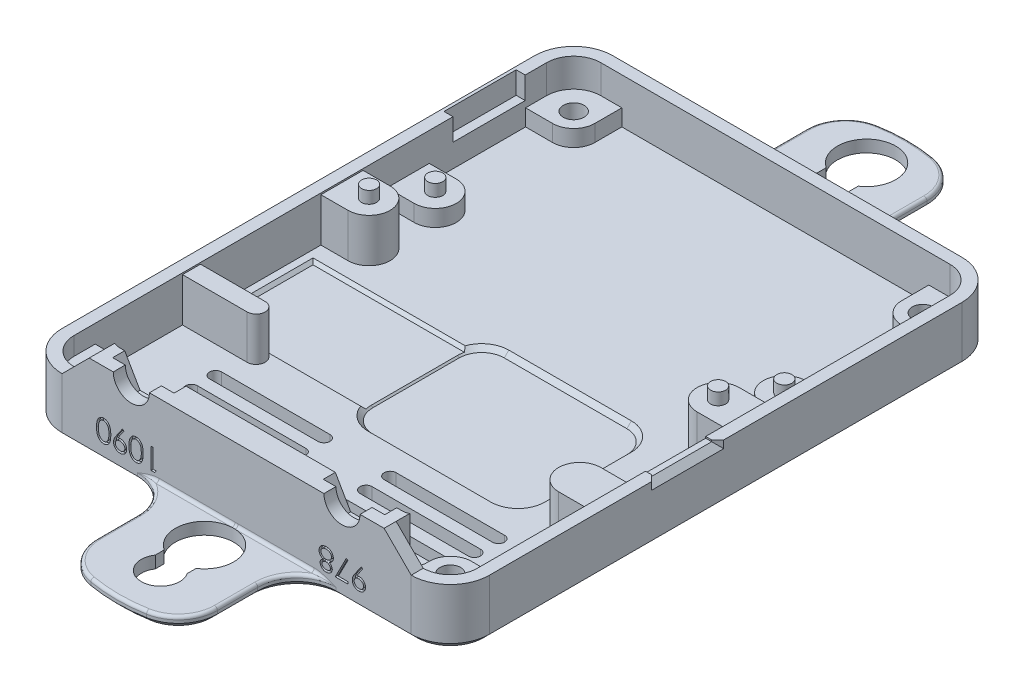
SolidWorks part; units mm, degrees
ref_plane "Front Plane" through (0, 0, 0) normal (0, 0, 1) x (1, 0, 0)
ref_plane "Top Plane" through (0, 0, 0) normal (0, 1, 0) x (1, 0, 0)
ref_plane "Right Plane" through (0, 0, 0) normal (1, 0, 0) x (0, 0, -1)
sketch "Sketch1" plane through (0, 0, 0) normal (0, 1, 0) x (1, 0, 0)
  line L0 (-33.8462, -25.5532) -> (31.1538, -25.5532)
  line L1 (-33.8462, 38.4468) -> (31.1538, 38.4468)
  line L2 (-33.8462, 38.4468) -> (-33.8462, 8.4468)
  line L3 (-33.8462, 8.4468) -> (31.1538, 8.4468)
  line L4 (31.1538, 38.4468) -> (31.1538, 8.4468)
  line L5 (-30.3462, 34.9468) -> (27.6538, 34.9468)
  line L6 (-30.3462, 34.9468) -> (-30.3462, 11.9468)
  line L7 (-30.3462, 11.9468) -> (27.6538, 11.9468)
  line L8 (27.6538, 34.9468) -> (27.6538, 11.9468)
  line L9 (-30.3462, 0.9468) -> (27.6538, 0.9468)
  line L10 (-30.3462, 0.9468) -> (-30.3462, -22.0532)
  line L11 (-33.8462, 4.4468) -> (31.1538, 4.4468)
  line L12 (-33.8462, 4.4468) -> (-33.8462, -25.5532)
  line L13 (-30.3462, -22.0532) -> (27.6538, -22.0532)
  line L14 (31.1538, 4.4468) -> (31.1538, -25.5532)
  line L15 (27.6538, 0.9468) -> (27.6538, -22.0532)
  line L16 (-37.9161, 25.3468) -> (-35.3276, 25.3468)
  line L17 (7.5538, 7.5472) -> (7.5538, 6.2645)
  line L18 (20.1538, 7.5472) -> (20.1538, 6.2645)
  dimension "D1" = 65
  dimension "D2" = 30
  dimension "D3" = 58
  dimension "D4" = 23
  dimension "D5" = 3.5
  dimension "D6" = 3.5
  dimension "D7" = 65
  dimension "D8" = 30
  dimension "D9" = 58
  dimension "D10" = 23
  dimension "D11" = 3.5
  dimension "D12" = 3.5
  dimension "D13" = 4
  dimension "D14" = 16.9
  dimension "D15" = 41.4
  dimension "D16" = 54
sketch "Sketch2" plane through (0, 0, 0) normal (0, 1, 0) x (1, 0, 0)
  line L0 (-33.8462, 38.4468) -> (-33.8462, 8.4468) construction
  line L1 (-30.3462, 39.4468) -> (27.6538, 39.4468)
  line L2 (-34.8462, 34.9468) -> (-34.8462, -43.5532)
  line L3 (-30.3462, -48.0532) -> (27.6538, -48.0532)
  line L4 (32.1538, 34.9468) -> (32.1538, -43.5532)
  line L5 (-33.8462, 38.4468) -> (31.1538, 38.4468) construction
  line L6 (31.1538, 38.4468) -> (31.1538, 8.4468) construction
  line L7 (-30.3462, 41.4468) -> (27.6538, 41.4468)
  line L8 (34.1538, 34.9468) -> (34.1538, -43.5532)
  line L9 (-30.3462, -50.0532) -> (27.6538, -50.0532)
  line L10 (-36.8462, 34.9468) -> (-36.8462, -43.5532)
  line L11 (-34.8462, 39.4468) -> (32.1538, 39.4468) construction
  line L12 (-34.8462, 39.4468) -> (-34.8462, -48.0532) construction
  line L13 (-36.8462, 41.4468) -> (-36.8462, -50.0532) construction
  line L14 (-36.8462, 41.4468) -> (34.1538, 41.4468) construction
  line L15 (32.1538, 39.4468) -> (32.1538, -48.0532) construction
  line L16 (34.1538, 41.4468) -> (34.1538, -50.0532) construction
  line L17 (-36.8462, -50.0532) -> (34.1538, -50.0532) construction
  line L18 (-34.8462, -48.0532) -> (32.1538, -48.0532) construction
  arc A0 (-30.3462, 39.4468) -> (-34.8462, 34.9468) centre (-30.3462, 34.9468) ccw
  arc A1 (-36.8462, 34.9468) -> (-30.3462, 41.4468) centre (-30.3462, 34.9468) cw
  arc A2 (32.1538, 34.9468) -> (27.6538, 39.4468) centre (27.6538, 34.9468) ccw
  arc A3 (34.1538, 34.9468) -> (27.6538, 41.4468) centre (27.6538, 34.9468) ccw
  arc A4 (27.6538, -50.0532) -> (34.1538, -43.5532) centre (27.6538, -43.5532) ccw
  arc A5 (-36.8462, -43.5532) -> (-30.3462, -50.0532) centre (-30.3462, -43.5532) ccw
  arc A6 (27.6538, -48.0532) -> (32.1538, -43.5532) centre (27.6538, -43.5532) ccw
  arc A7 (-30.3462, -48.0532) -> (-34.8462, -43.5532) centre (-30.3462, -43.5532) cw
  dimension "D6" = 4.5
  dimension "D7" = 6.5
  dimension "D8" = 4.5
  dimension "D9" = 6.5
  dimension "D10" = 6.5
  dimension "D11" = 4.5
  dimension "D1" = 1
  dimension "D2" = 1
  dimension "D3" = 1
  dimension "D4" = 87.5
  dimension "D5" = 2
extrude "Boss-Extrude1" add sketch "Sketch2" along normal blind 9.5
sketch "Sketch3" plane through (0, 0, 0) normal (0, 1, 0) x (1, 0, 0)
  line L0 (-30.3462, -48.0532) -> (27.6538, -48.0532)
  line L1 (-30.3462, 39.4468) -> (27.6538, 39.4468)
  line L2 (-34.8462, 34.9468) -> (-34.8462, -43.5532)
  line L4 (32.1538, 34.9468) -> (32.1538, -43.5532)
  arc A0 (-34.8462, -43.5532) -> (-30.3462, -48.0532) centre (-30.3462, -43.5532) ccw
  arc A1 (27.6538, -48.0532) -> (32.1538, -43.5532) centre (27.6538, -43.5532) ccw
  arc A2 (32.1538, 34.9468) -> (27.6538, 39.4468) centre (27.6538, 34.9468) ccw
  arc A3 (-30.3462, 39.4468) -> (-34.8462, 34.9468) centre (-30.3462, 34.9468) ccw
  dimension "D1" = 4.5
  dimension "D2" = 4.5
  dimension "D3" = 87.5
extrude "Boss-Extrude2" add sketch "Sketch3" along normal blind 2
sketch "Sketch4" plane through (0, 2, 0) normal (0, 1, 0) x (1, 0, 0)
  line L1 (-4.1234, -3.5548) -> (16.2444, -3.5548)
  line L2 (-7.1234, -6.5548) -> (-7.1234, -20.9191)
  line L3 (-4.1234, -23.9191) -> (16.2444, -23.9191)
  line L4 (19.2444, -6.5548) -> (19.2444, -20.9191)
  arc A0 (16.2444, -23.9191) -> (19.2444, -20.9191) centre (16.2444, -20.9191) ccw
  arc A1 (-7.1234, -20.9191) -> (-4.1234, -23.9191) centre (-4.1234, -20.9191) ccw
  arc A2 (19.2444, -6.5548) -> (16.2444, -3.5548) centre (16.2444, -6.5548) ccw
  arc A3 (-7.1234, -6.5548) -> (-4.1234, -3.5548) centre (-4.1234, -6.5548) cw
  dimension "D1" = 3
extrude "Cut-Extrude2" cut sketch "Sketch4" against normal blind 0.75
chamfer "Chamfer1" distance 1.5 angle 45 8 edges at (6.0605, 2, 23.9191) (18.3657, 2, 23.0404) (-6.2447, 2, 23.0404) (19.2444, 2, 13.7369) (-7.1234, 2, 13.7369) (18.3657, 2, 4.4335) (-6.2447, 2, 4.4335) (6.0605, 2, 3.5548) tangent propagation no
sketch "Sketch5" plane through (0, 1.25, 0) normal (0, 1, 0) x (1, 0, 0)
  line L0 (-30.3462, 4.4468) -> (-34.8462, 4.4468)
  line L1 (-34.8462, 34.9468) -> (-34.8462, -43.5532) construction
  line L2 (-34.8462, 4.4468) -> (-34.8462, -2.5532)
  line L3 (-34.8462, -2.5532) -> (-30.3462, -2.5532)
  line L4 (27.6538, 4.4468) -> (32.1538, 4.4468)
  line L5 (32.1538, -43.5532) -> (32.1538, 34.9468) construction
  line L6 (32.1538, 4.4468) -> (32.1538, -2.5532)
  line L7 (32.1538, -43.5532) -> (32.1538, 34.9468) construction
  line L8 (32.1538, -2.5532) -> (27.6538, -2.5532)
  line L9 (32.1538, -18.5532) -> (32.1538, -25.5532)
  line L10 (-34.8462, -25.5532) -> (-24.1094, -25.5532)
  line L11 (-34.8462, -25.5532) -> (-34.8462, -22.5532)
  line L12 (-34.8462, -22.5532) -> (-24.1094, -22.5532)
  line L13 (32.1538, -25.5532) -> (27.6538, -25.5532)
  line L14 (27.6538, -18.5532) -> (32.1538, -18.5532)
  arc A0 (-30.3462, -2.5532) -> (-30.3462, 4.4468) centre (-30.3462, 0.9468) ccw
  arc A1 (27.6538, 4.4468) -> (27.6538, -2.5532) centre (27.6538, 0.9468) ccw
  arc A2 (-24.1094, -22.5532) -> (-24.1094, -25.5532) centre (-24.1094, -24.0532) cw
  arc A3 (27.6538, -18.5532) -> (27.6538, -25.5532) centre (27.6538, -22.0532) ccw
  dimension "D1" = 3
extrude "Boss-Extrude3" add sketch "Sketch5" along normal blind 8
sketch "Sketch6" plane through (0, 1.25, 0) normal (0, 1, 0) x (1, 0, 0)
  line L0 (-30.3462, 15.4468) -> (-34.8462, 15.4468)
  line L1 (-34.8462, 34.9468) -> (-34.8462, -43.5532) construction
  line L2 (-34.8462, 15.4468) -> (-34.8462, 8.4468)
  line L3 (-34.8462, 34.9468) -> (-34.8462, 4.4468) construction
  line L4 (-34.8462, 8.4468) -> (-30.3462, 8.4468)
  line L5 (-26.8462, 34.9468) -> (-26.8462, 39.4468)
  line L6 (27.6538, 39.4468) -> (-30.3462, 39.4468) construction
  line L7 (-26.8462, 39.4468) -> (-30.3462, 39.4468)
  line L8 (-30.3462, 31.4468) -> (-34.8462, 31.4468)
  line L9 (-34.8462, 31.4468) -> (-34.8462, 34.9468)
  line L10 (24.1538, 34.9468) -> (24.1538, 39.4468)
  line L11 (24.1538, 39.4468) -> (27.6538, 39.4468)
  line L12 (27.6538, 31.4468) -> (32.1538, 31.4468)
  line L13 (32.1538, 4.4468) -> (32.1538, 34.9468) construction
  line L14 (32.1538, 31.4468) -> (32.1538, 34.9468)
  line L15 (27.6538, 15.4468) -> (32.1538, 15.4468)
  line L16 (27.6538, 8.4468) -> (32.1538, 8.4468)
  line L17 (32.1538, -43.5532) -> (32.1538, 34.9468) construction
  line L18 (32.1538, 8.4468) -> (32.1538, 15.4468)
  arc A0 (-30.3462, 31.4468) -> (-26.8462, 34.9468) centre (-30.3462, 34.9468) ccw
  arc A1 (24.1538, 34.9468) -> (27.6538, 31.4468) centre (27.6538, 34.9468) ccw
  arc A2 (27.6538, 15.4468) -> (27.6538, 8.4468) centre (27.6538, 11.9468) ccw
  arc A3 (-30.3462, 8.4468) -> (-30.3462, 15.4468) centre (-30.3462, 11.9468) ccw
  arc A4 (-30.3462, 39.4468) -> (-34.8462, 34.9468) centre (-30.3462, 34.9468) ccw
  arc A5 (32.1538, 34.9468) -> (27.6538, 39.4468) centre (27.6538, 34.9468) ccw
  dimension "D1" = 4.5
  dimension "D2" = 4.5
extrude "Boss-Extrude4" add sketch "Sketch6" along normal blind 3.5
sketch "Sketch7" plane through (0, 0, 50.0532) normal (0, 0, 1) x (1, 0, 0)
  line L0 (27.6538, 9.5) -> (-30.3462, 9.5)
  line L3 (13.1538, 14) -> (-15.8462, 14)
  line L4 (-1.3462, 9.5) -> (-1.3462, 14) construction
  line L5 (-30.3462, 9.5) -> (27.6538, 9.5) construction
  line L6 (-30.3462, 9.5) -> (-25.8462, 14)
  line L7 (-25.8462, 14) -> (-21.8462, 14)
  line L9 (23.1538, 14) -> (19.1538, 14)
  line L13 (27.6538, 9.5) -> (23.1538, 14)
  arc A0 (-21.8462, 14) -> (-15.8462, 14) centre (-18.8462, 14) ccw
  arc A1 (13.1538, 14) -> (19.1538, 14) centre (16.1538, 14) ccw
  dimension "D2" = 35
  dimension "D1" = 4.5
  dimension "D6" = 3
  dimension "D7" = 3
  dimension "D3" = 4.5
  dimension "D4" = 45
  dimension "D5" = 4.5
extrude "Boss-Extrude5" add sketch "Sketch7" against normal up to vertex (2 mm away) up to point (-30.3462, 9.5, 48.0532)
sketch "Sketch10" plane through (0, 2, 0) normal (0, 1, 0) x (1, 0, 0)
  line L0 (-30.3462, -40.0532) -> (-34.8462, -40.0532)
  line L1 (27.6538, -40.0532) -> (32.1538, -40.0532)
  line L2 (-34.8462, -40.0532) -> (-34.8462, -43.5532)
  line L3 (-26.8462, -43.5532) -> (-26.8462, -48.0532)
  line L4 (32.1538, -43.5532) -> (32.1538, 34.9468) construction
  line L5 (-26.8462, -48.0532) -> (-30.3462, -48.0532)
  line L6 (32.1538, -40.0532) -> (32.1538, -43.5532)
  line L7 (24.1538, -43.5532) -> (24.1538, -48.0532)
  line L8 (-30.3462, -48.0532) -> (27.6538, -48.0532) construction
  line L9 (24.1538, -48.0532) -> (27.6538, -48.0532)
  line L10 (-4.8462, -43.5532) -> (-4.8462, -48.0532)
  line L11 (-4.8462, -48.0532) -> (2.1538, -48.0532)
  line L12 (2.1538, -48.0532) -> (2.1538, -43.5532)
  arc A0 (-34.8462, -43.5532) -> (-30.3462, -48.0532) centre (-30.3462, -43.5532) ccw
  arc A1 (-26.8462, -43.5532) -> (-30.3462, -40.0532) centre (-30.3462, -43.5532) ccw
  arc A2 (32.1538, -43.5532) -> (27.6538, -48.0532) centre (27.6538, -43.5532) cw
  arc A3 (27.6538, -48.0532) -> (32.1538, -43.5532) centre (27.6538, -43.5532) ccw construction
  arc A4 (27.6538, -40.0532) -> (24.1538, -43.5532) centre (27.6538, -43.5532) ccw
  arc A5 (2.1538, -43.5532) -> (-4.8462, -43.5532) centre (-1.3462, -43.5532) ccw
extrude "Boss-Extrude6" add sketch "Sketch10" along normal offset from surface (4.5 mm away) 3 up to face at (-1.3462, 9.5, 4.3032)
sketch "Sketch11" plane through (34.1538, 0, 0) normal (1, 0, 0) x (0, 0, -1)
  line L1 (-15.6251, 10.2426) -> (-5.6251, 10.2426)
  line L2 (-15.6251, 10.2426) -> (-15.6251, 9.2424)
  line L3 (-15.6251, 9.2424) -> (-5.6251, 9.2424)
  line L4 (-5.6251, 10.2426) -> (-5.6251, 9.2424)
extrude "Cut-Extrude3" cut sketch "Sketch11" against normal up to next
chamfer "Chamfer2" distance 1 angle 45 3 edges at (34.1538, 9.3712, 5.6251) (34.1538, 9.3712, 15.6251) (34.1538, 9.2424, 10.6251)
sketch "Sketch12" plane through (-34.8462, 0, 0) normal (-1, 0, 0) x (0, 0, 1)
  line L1 (-31.3918, 9.8223) -> (-19.3918, 9.8223)
  line L2 (-31.3918, 9.8223) -> (-31.3918, 5.8223)
  line L3 (-31.3918, 5.8223) -> (-19.3918, 5.8223)
  line L4 (-19.3918, 9.8223) -> (-19.3918, 5.8223)
  line L5 (-31.3918, 9.8223) -> (-19.3918, 5.8223) construction
  line L6 (-31.3918, 5.8223) -> (-19.3918, 9.8223) construction
  point P0 (-25.3918, 7.8223)
  dimension "D1" = 12
  dimension "D2" = 4
sketch "Sketch34" plane through (0, 2, 0) normal (0, 1, 0) x (1, 0, 0)
  line L1 (-5.843, -6.5548) -> (-32.1578, -6.5548)
  line L2 (-5.843, -6.5548) -> (-5.843, -20.9191)
  line L3 (-5.843, -20.9191) -> (-32.1578, -20.9191)
  line L4 (-32.1578, -6.5548) -> (-32.1578, -20.9191)
extrude "Cut-Extrude5" cut sketch "Sketch34" against normal blind 0.5
chamfer "Chamfer5" distance 1.5 angle 45 3 edges at (-20.3906, 2, 20.9191) (-32.1578, 2, 13.7369) (-20.3906, 2, 6.5548)
extrude "Cut-Extrude6" cut sketch "Sketch12" along normal blind 1.5
sketch "Sketch36" plane through (0, 0, 0) normal (0, -1, 0) x (1, 0, 0)
  line L0 (-5.6411, -4.4361) -> (-6.5788, -2.9987)
  line L1 (-5.6135, -17.5484) -> (-6.5451, -18.9896)
  line L2 (2.8733, -4.4181) -> (3.8048, -2.9769)
  line L3 (2.9009, -17.5304) -> (3.8385, -18.9678)
  line L4 (-14.7411, -31.67) -> (-15.5841, -32.9742)
  line L5 (-9.464, -23.5056) -> (-10.3585, -24.8894)
  line L6 (-9.5167, 1.5049) -> (-10.4169, 2.885)
  line L7 (-14.8281, 9.647) -> (-15.6766, 10.9477)
  line L8 (12.0008, 9.7035) -> (12.8438, 11.0078)
  line L9 (6.7238, 1.5391) -> (7.6182, 2.9229)
  line L10 (6.7764, -23.4714) -> (7.6767, -24.8515)
  line L11 (12.0878, -31.6135) -> (12.9363, -32.9142)
  line L12 (-3.5903, -40.4468) -> (-2.2438, -13.3244)
  line L13 (0.898, -40.4468) -> (-0.192, -13.3244)
  line L14 (-3.5903, -40.4468) -> (0.898, -40.4468)
  line L15 (-2.2438, -13.3244) -> (-0.192, -13.3244)
  arc A0 (12.9363, -32.9142) -> (12.8438, 11.0078) centre (-1.3701, -10.9832) ccw
  arc A1 (12.0878, -31.6135) -> (12.0008, 9.7035) centre (-1.3701, -10.9832) ccw
  arc A2 (2.9009, -17.5304) -> (2.8733, -4.4181) centre (-1.3701, -10.9832) ccw
  arc A3 (3.8385, -18.9678) -> (3.8048, -2.9769) centre (-1.3701, -10.9832) ccw
  arc A4 (7.6767, -24.8515) -> (7.6182, 2.9229) centre (-1.3701, -10.9832) ccw
  arc A5 (6.7764, -23.4714) -> (6.7238, 1.5391) centre (-1.3701, -10.9832) ccw
  arc A6 (-15.6766, 10.9477) -> (-15.5841, -32.9742) centre (-1.3701, -10.9832) ccw
  arc A7 (-14.8281, 9.647) -> (-14.7411, -31.67) centre (-1.3701, -10.9832) ccw
  arc A8 (-10.4169, 2.885) -> (-10.3585, -24.8894) centre (-1.3701, -10.9832) ccw
  arc A9 (-9.5167, 1.5049) -> (-9.464, -23.5056) centre (-1.3701, -10.9832) ccw
  arc A10 (-6.5788, -2.9987) -> (-6.5451, -18.9896) centre (-1.3701, -10.9832) ccw
  arc A11 (-5.6411, -4.4361) -> (-5.6135, -17.5484) centre (-1.3701, -10.9832) ccw
extrude "Cut-Extrude8" cut sketch "Sketch36" against normal blind 0.4
sketch "Sketch37" plane through (0, 0, 0) normal (0, 1, 0) x (1, 0, 0)
  line L0 (-1.9008, 5.7134) -> (12.3211, -8.0776)
  line L1 (12.3211, -8.0776) -> (16.1409, -4.1385)
  line L2 (16.1409, -4.1385) -> (3.4609, 11.2426)
  line L3 (3.4609, 11.2426) -> (9.8009, 20.3663)
  line L4 (9.8009, 20.3663) -> (15.1149, 16.2462)
  line L5 (15.1149, 16.2462) -> (17.8041, 19.0194)
  line L6 (17.8041, 19.0194) -> (12.774, 24.201)
  line L7 (12.774, 24.201) -> (13.7731, 25.4896)
  line L8 (13.7731, 25.4896) -> (13.4862, 25.712)
  line L9 (-1.9008, 5.7134) -> (-4.5225, 3.5521)
  line L10 (-4.5225, 3.5521) -> (-6.7547, 2.0307)
  line L11 (-6.7547, 2.0307) -> (-8.3897, 1.1526)
  line L12 (-8.3897, 1.1526) -> (-9.0215, 1.5916)
  line L13 (-9.0215, 1.5916) -> (-9.9767, 1.0787)
  line L14 (-9.9767, 1.0787) -> (-10.839, 0.7913)
  line L15 (-10.839, 0.7913) -> (-11.0799, 0.7913)
  line L16 (13.4862, 25.712) -> (-11.0799, 0.7913) construction
  line L17 (-11.0833, 1.0321) -> (-11.0799, 0.7913)
  line L18 (-10.8083, 1.8985) -> (-11.0833, 1.0321)
  line L19 (-10.3091, 2.8609) -> (-10.8083, 1.8985)
  line L20 (-10.7571, 3.4863) -> (-10.3091, 2.8609)
  line L21 (-9.9026, 5.1337) -> (-10.7571, 3.4863)
  line L22 (-8.4134, 7.3875) -> (-9.9026, 5.1337)
  line L23 (-6.2899, 10.0399) -> (-8.4134, 7.3875)
  line L24 (13.2596, 25.9958) -> (13.4862, 25.712)
  line L25 (11.9855, 24.9783) -> (13.2596, 25.9958)
  line L26 (6.7323, 29.9336) -> (11.9855, 24.9783)
  line L27 (3.9979, 27.2049) -> (6.7323, 29.9336)
  line L28 (8.1938, 21.9505) -> (3.9979, 27.2049)
  line L29 (-0.8381, 15.4803) -> (8.1938, 21.9505)
  line L30 (-16.3994, 27.9385) -> (-0.8381, 15.4803)
  line L31 (-20.2833, 24.0627) -> (-16.3994, 27.9385)
  line L32 (-6.2899, 10.0399) -> (-20.2833, 24.0627)
extrude "Cut-Extrude14" cut sketch "Sketch37" along normal blind 0.4
sketch "Sketch38" plane through (0, 0, 48.0532) normal (0, 0, -1) x (-1, 0, 0)
  line L0 (-23.1538, 14) -> (-21.2558, 14)
  line L1 (-23.1538, 14) -> (-23.1538, 6.5)
  line L2 (16.2952, 9.5816) -> (21.3971, 9.5816)
  line L3 (26.8462, 2) -> (4.8462, 2) construction
  line L4 (-21.2558, 14) -> (-18.7048, 9.5816)
  line L5 (-18.7048, 9.5816) -> (-13.6029, 9.5816)
  line L6 (-13.6029, 9.5816) -> (-11.0519, 14)
  line L7 (-23.9027, 2) -> (-9.4512, 2)
  line L8 (21.3971, 9.5816) -> (23.9481, 14)
  line L9 (-19.9803, 16.2092) -> (-21.135, 14.2092) [skipped]
  line L10 (-14.8081, 18.4184) -> (-17.1175, 18.4184) [skipped]
  line L11 (-12.3274, 16.2092) -> (-13.4821, 18.2092) [skipped]
  line L12 (13.7442, 14) -> (16.2952, 9.5816)
  line L13 (25.8462, 14) -> (23.9481, 14)
  line L15 (13.7442, 14) -> (12.1436, 14)
  line L16 (-9.4512, 14) -> (12.1436, 14)
  line L17 (26.8462, 6.5) -> (25.8462, 6.5)
  line L18 (-24.1538, 6.5) -> (-23.1538, 6.5)
  line L20 (-9.4512, 14) -> (-11.0519, 14)
  line L22 (-24.1538, 6.5) -> (-24.1538, 2)
  line L23 (-24.1538, 2) -> (-23.9027, 2)
  line L25 (25.8462, 14) -> (25.8462, 6.5)
  line L27 (26.8462, 6.5) -> (26.8462, 2)
  line L28 (26.8462, 2) -> (-9.4512, 2)
  arc A0 (15.3313, 11.2512) -> (22.361, 11.2512) centre (18.8462, 14) ccw construction
  arc A2 (-19.6687, 11.2512) -> (-12.639, 11.2512) centre (-16.1538, 14) ccw construction
extrude "Boss-Extrude7" add sketch "Sketch38" along normal blind 2
sketch "Sketch39" plane through (0, 0, 50.0532) normal (0, 0, 1) x (1, 0, 0)
  line L0 (-25.8321, 6.4571) -> (-13.0275, 6.4571) construction
  line L1 (9.3531, 6.4571) -> (23.0562, 6.4571) construction
  text T0 "1090"
  text T1 "978"
extrude "Cut-Extrude15" cut sketch "Sketch39" against normal blind 0.5
sketch "Sketch40" plane through (0, 4.75, 0) normal (0, 1, 0) x (1, 0, 0)
  circle A0 centre (-30.3462, 11.9468) radius 1.25
  circle A1 centre (27.6538, 11.9468) radius 1.25
  dimension "D1" = 2.5
  dimension "D2" = 2.5
extrude "Boss-Extrude8" add sketch "Sketch40" along normal blind 2
sketch "Sketch41" plane through (0, 9.25, 0) normal (0, 1, 0) x (1, 0, 0)
  circle A0 centre (-30.3462, 0.9468) radius 1.25
  circle A2 centre (27.6538, 0.9468) radius 1.25
  dimension "D1" = 2.5
  dimension "D2" = 2.5
extrude "Boss-Extrude9" add sketch "Sketch41" along normal blind 2
fillet "Fillet1" radius 2 6 edges at (13.1538, 2, 46.0532) (-15.8462, 2, 46.0532) (-4.8462, 4.25, 46.0532) (24.1538, 4.25, 46.0532) (2.1538, 4.25, 46.0532) (-26.8462, 4.25, 46.0532)
hole_wizard "CSK for #4 Flat Head Socket Cap Screw1" positions "Sketch43" profile "Sketch42" countersink size "#4" standard "ANSI Inch" end condition through all
sketch "Sketch43" plane through (0, 0, 0) normal (0, -1, 0) x (-1, 0, 0)
  point P2 (30.3462, -43.5532)
  point P6 (1.3462, -43.5532)
  point P10 (-27.6538, -43.5532)
  point P14 (30.3462, 34.9468)
  point P18 (-27.6538, 34.9468)
sketch "Sketch42" plane through (-30.3462, 0, 43.5532) normal (1, 0, 0) x (0, 0, -1)
  line L0 (0, 0) -> (0, 14)
  line L1 (0, 14) -> (1.7272, 14)
  line L2 (1.7272, 14) -> (1.7272, 1.8805)
  line L3 (1.7272, 1.8805) -> (3.3619, 0)
  line L5 (3.3619, 0) -> (0, 0)
  line L6 (-1.7272, 1.8805) -> (-3.3619, 0) construction
  line L11 (0, -6.35) -> (0, 107.95) construction
  dimension "Thru Hole Dia." = 3.4544
  dimension "Thru Hole Depth" = 14
  dimension "Near C'Sink Dia." = 6.7237
  dimension "Near C'Sink Angle" = 82
sketch "Sketch44" plane through (0, 2, 0) normal (0, 1, 0) x (1, 0, 0)
  line L0 (-24.8462, -38.0532) -> (-6.8462, -38.0532) construction
  line L1 (-24.8462, -37.0532) -> (-6.8462, -37.0532)
  line L2 (-24.8462, -39.0532) -> (-6.8462, -39.0532)
  line L3 (-6.8462, -46.0532) -> (-24.8462, -46.0532) construction
  line L4 (-24.8462, -34.0532) -> (-6.8462, -34.0532) construction
  line L5 (-24.8462, -33.0532) -> (-6.8462, -33.0532)
  line L6 (-24.8462, -35.0532) -> (-6.8462, -35.0532)
  line L7 (-24.8462, -30.0532) -> (-6.8462, -30.0532) construction
  line L8 (-24.8462, -29.0532) -> (-6.8462, -29.0532)
  line L9 (-24.8462, -31.0532) -> (-6.8462, -31.0532)
  line L10 (4.1538, -38.0532) -> (22.1538, -38.0532) construction
  line L11 (4.1538, -37.0532) -> (22.1538, -37.0532)
  line L12 (4.1538, -39.0532) -> (22.1538, -39.0532)
  line L13 (4.1538, -34.0532) -> (22.1538, -34.0532) construction
  line L14 (4.1538, -33.0532) -> (22.1538, -33.0532)
  line L15 (4.1538, -35.0532) -> (22.1538, -35.0532)
  line L16 (4.1538, -30.0532) -> (22.1538, -30.0532) construction
  line L17 (4.1538, -29.0532) -> (22.1538, -29.0532)
  line L18 (4.1538, -31.0532) -> (22.1538, -31.0532)
  arc A0 (-24.8462, -37.0532) -> (-24.8462, -39.0532) centre (-24.8462, -38.0532) ccw
  arc A1 (-6.8462, -39.0532) -> (-6.8462, -37.0532) centre (-6.8462, -38.0532) ccw
  arc A2 (-24.8462, -33.0532) -> (-24.8462, -35.0532) centre (-24.8462, -34.0532) ccw
  arc A3 (-6.8462, -35.0532) -> (-6.8462, -33.0532) centre (-6.8462, -34.0532) ccw
  arc A4 (-24.8462, -29.0532) -> (-24.8462, -31.0532) centre (-24.8462, -30.0532) ccw
  arc A5 (-6.8462, -31.0532) -> (-6.8462, -29.0532) centre (-6.8462, -30.0532) ccw
  arc A6 (4.1538, -37.0532) -> (4.1538, -39.0532) centre (4.1538, -38.0532) ccw
  arc A7 (22.1538, -39.0532) -> (22.1538, -37.0532) centre (22.1538, -38.0532) ccw
  arc A8 (4.1538, -33.0532) -> (4.1538, -35.0532) centre (4.1538, -34.0532) ccw
  arc A9 (22.1538, -35.0532) -> (22.1538, -33.0532) centre (22.1538, -34.0532) ccw
  arc A10 (4.1538, -29.0532) -> (4.1538, -31.0532) centre (4.1538, -30.0532) ccw
  arc A11 (22.1538, -31.0532) -> (22.1538, -29.0532) centre (22.1538, -30.0532) ccw
  point P2 (-15.8462, -38.0532)
  point P12 (-15.8462, -34.0532)
  point P19 (-15.8462, -30.0532)
  point P25 (13.1538, -38.0532)
  point P32 (13.1538, -34.0532)
  point P39 (13.1538, -30.0532)
  dimension "D1" = 8
  dimension "D2" = 3
extrude "Cut-Extrude16" cut sketch "Sketch44" against normal through all
sketch "Sketch45" plane through (0, 0, 0) normal (0, -1, 0) x (1, 0, 0)
  line L0 (1.3115, 60.9145) -> (1.3115, 59.4341)
  line L1 (-11.3462, 50.0532) -> (8.6538, 50.0532)
  line L2 (-11.3462, 50.0532) -> (-11.3462, 68.0939)
  line L3 (1.3115, 60.9145) -> (1.3115, 59.4341)
  line L4 (8.6538, 50.0532) -> (8.6538, 68.0939)
  line L8 (-1.3462, 62.6968) -> (-1.3462, 55.3875)
  line L9 (-4.0038, 60.9145) -> (-4.0038, 59.4341)
  line L10 (-11.3462, 50.0532) -> (-11.3462, 68.0939)
  line L11 (-4.0038, 60.9145) -> (-4.0038, 59.4341)
  line L12 (8.6538, 50.0532) -> (8.6538, 68.0939)
  line L13 (-11.3462, 50.0532) -> (-11.3462, 68.0939)
  line L14 (1.3115, 60.9145) -> (1.3115, 59.4341)
  line L15 (8.6538, 50.0532) -> (8.6538, 68.0939)
  line L16 (1.3115, 60.9145) -> (1.3115, 59.4341)
  line L17 (-11.3462, 50.0532) -> (-11.3462, 68.0939)
  line L18 (-4.0038, 60.9145) -> (-4.0038, 59.4341)
  line L19 (8.6538, 50.0532) -> (8.6538, 68.0939)
  line L20 (-4.0038, 60.9145) -> (-4.0038, 59.4341)
  line L21 (8.6538, -41.4468) -> (8.6538, -59.4876)
  line L22 (-11.3462, -41.4468) -> (8.6538, -41.4468)
  line L23 (-11.3462, -41.4468) -> (-11.3462, -59.4876)
  line L24 (-1.3462, -47.3017) -> (-1.3462, -54.611)
  line L25 (-4.0038, -49.084) -> (-4.0038, -50.5644)
  line L26 (1.3115, -49.084) -> (1.3115, -50.5644)
  arc A0 (8.6538, 68.0939) -> (-11.3462, 68.0939) centre (-1.3462, 43.5532) ccw
  arc A1 (1.3115, 60.9145) -> (-4.0038, 60.9145) centre (-1.3462, 62.6968) ccw
  arc A2 (-4.0038, 59.4341) -> (1.3115, 59.4341) centre (-1.3462, 55.3875) ccw
  arc A3 (8.6538, -59.4876) -> (-11.3462, -59.4876) centre (-1.3462, -34.9468) cw
  arc A4 (1.3115, -49.084) -> (-4.0038, -49.084) centre (-1.3462, -47.3017) ccw
  arc A5 (-4.0038, -50.5644) -> (1.3115, -50.5644) centre (-1.3462, -54.611) ccw
  dimension "D1" = 20
extrude "Boss-Extrude10" add sketch "Sketch45" against normal blind 2 contours A3 L21 L22 L23 | L4 A0 L2 L1 A2 L9 A1 L0 region at (-11.0633, 0, 59.0735) region at (8.371, 0, -50.4672)
fillet "Fillet2" radius 6.5 8 edges at (8.6538, 1, -41.4468) (8.6538, 1, -59.4876) (-11.3462, 1, -59.4876) (-11.3462, 1, -41.4468) (-11.3462, 1, 50.0532) (-11.3462, 1, 68.0939) (8.6538, 1, 68.0939) (8.6538, 1, 50.0532)
chamfer "Chamfer6" distance 1 angle 45 24 edges at (34.1538, 0, 4.3032) (32.25, 0, -39.543) (32.25, 0, 48.1493) (21.4038, 0, -41.4468) (21.4038, 0, 50.0532) (10.5577, 0, -43.3507) (10.5577, 0, 51.957) (8.6538, 0, -51.2925) (8.6538, 0, 59.8988) (7.136, 0, -58.8129) (7.136, 0, 67.4192) (-1.3462, 0, -61.4468) (-1.3462, 0, 70.0532) (-9.8283, 0, -58.8129) (-9.8283, 0, 67.4192) (-11.3462, 0, -51.2925) (-11.3462, 0, 59.8988) (-13.25, 0, -43.3507) (-13.25, 0, 51.957) (-24.0962, 0, -41.4468) (-24.0962, 0, 50.0532) (-34.9423, 0, -39.543) (-34.9423, 0, 48.1493) (-36.8462, 0, 4.3032)
fillet "Fillet3" radius 0.5 8 edges at (10.5577, 2, -43.3507) (8.6538, 2, -51.2925) (7.136, 2, -58.8129) (-13.25, 2, -43.3507) (-11.3462, 2, -51.2925) (-9.8283, 2, -58.8129) (-1.3462, 2, -61.4468) (-1.3462, 2, -41.4468)
fillet "Fillet4" radius 0.5 8 edges at (10.5577, 2, 51.957) (8.6538, 2, 59.8988) (7.136, 2, 67.4192) (-13.25, 2, 51.957) (-11.3462, 2, 59.8988) (-9.8283, 2, 67.4192) (-1.3462, 2, 70.0532) (-1.3462, 2, 50.0532)
